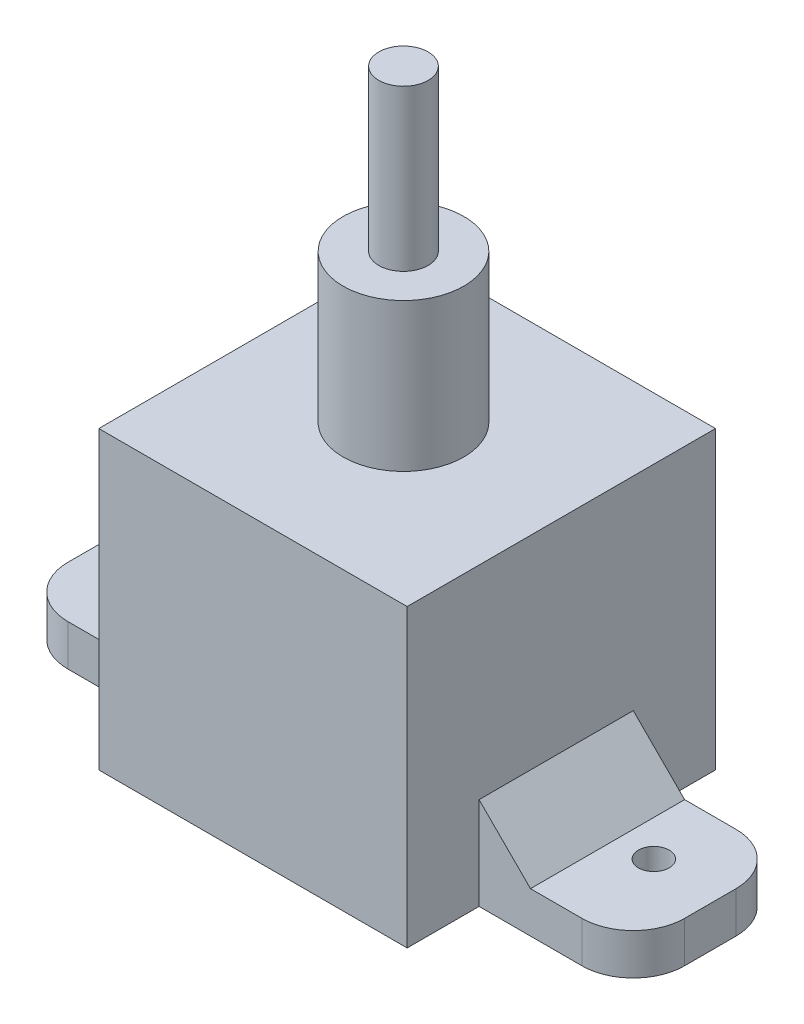
SolidWorks part; units mm, degrees
ref_plane "Спереди" through (0, 0, 0) normal (0, 0, 1) x (1, 0, 0)
ref_plane "Сверху" through (0, 0, 0) normal (0, 1, 0) x (1, 0, 0)
ref_plane "Справа" through (0, 0, 0) normal (1, 0, 0) x (0, 0, -1)
other "Configuration Table"
sketch "Эскиз1" plane through (0, 0, 0) normal (0, 1, 0) x (1, 0, 0)
  line L1 (-14.2865, 14.6433) -> (15.7135, 14.6433)
  line L2 (-14.2865, 14.6433) -> (-14.2865, -15.3567)
  line L3 (-14.2865, -15.3567) -> (15.7135, -15.3567)
  line L4 (15.7135, 14.6433) -> (15.7135, -15.3567)
  dimension "D1" = 30
  dimension "D2" = 30
extrude "высота " add sketch "Эскиз1" along normal blind 28.77
sketch "Эскиз2" plane through (0, 28.77, 0) normal (0, 1, 0) x (1, 0, 0)
  circle A0 centre (0, 0) radius 5.875
  dimension "D1" = 11.75
sketch "Эскиз3" plane through (0, 0, 0) normal (0, 0, 1) x (1, 0, 0)
  line L0 (0, 49.97) -> (0, -1.7648) construction
extrude "Бобышка-Вытянуть2" add sketch "Эскиз2" along normal blind 14.4 contours A0
sketch "Эскиз4" plane through (0, 43.17, 0) normal (0, 1, 0) x (1, 0, 0)
  circle A0 centre (0, 0) radius 2.4
  dimension "D1" = 4.8
extrude "Бобышка-Вытянуть3" add sketch "Эскиз4" along normal blind 15.6
sketch "Эскиз5" plane through (0, 0, 0) normal (0, -1, 0) x (1, 0, 0)
  line L0 (15.7135, 15.3567) -> (15.7135, -14.6433) construction
  line L1 (15.7135, 8.3567) -> (25.7135, 8.3567)
  line L2 (15.7135, 8.3567) -> (15.7135, -6.6433)
  line L3 (15.7135, -6.6433) -> (25.7135, -6.6433)
  line L4 (30.7135, 3.3567) -> (30.7135, -1.6433)
  line L5 (15.7135, -14.6433) -> (-14.2865, -14.6433) construction
  line L6 (0, 0) -> (0, -14.6433) construction
  line L12 (-14.2865, -14.6433) -> (-14.2865, 15.3567) construction
  line L13 (-14.2865, 8.3567) -> (-24.2865, 8.3567)
  line L14 (-14.2865, 8.3567) -> (-14.2865, -6.6433)
  line L15 (-14.2865, -6.6433) -> (-24.2865, -6.6433)
  line L16 (-29.2865, 3.3567) -> (-29.2865, -1.6433)
  arc A0 (-29.2865, 3.3567) -> (-24.2865, 8.3567) centre (-24.2865, 3.3567) cw
  arc A1 (-24.2865, -6.6433) -> (-29.2865, -1.6433) centre (-24.2865, -1.6433) cw
  arc A2 (30.7135, 3.3567) -> (25.7135, 8.3567) centre (25.7135, 3.3567) ccw
  arc A3 (30.7135, -1.6433) -> (25.7135, -6.6433) centre (25.7135, -1.6433) cw
  point P19 (-29.2865, 8.3567)
  point P22 (-29.2865, -6.6433)
  point P25 (30.7135, 8.3567)
  point P28 (30.7135, -6.6433)
  dimension "D7" = 5
  dimension "D8" = 5
  dimension "D9" = 5
  dimension "D10" = 5
  dimension "D1" = 15
  dimension "D2" = 15
  dimension "D3" = 8
  dimension "D4" = 15
  dimension "D5" = 15
  dimension "D6" = 8
extrude "Бобышка-Вытянуть4" add sketch "Эскиз5" against normal blind 4
sketch "Эскиз6" plane through (0, 4, 0) normal (0, 1, 0) x (1, 0, 0)
  line L0 (30.7135, 1.6433) -> (30.7135, -3.3567) construction
  line L1 (15.7135, 6.6433) -> (25.7135, 6.6433) construction
  line L2 (-24.2865, 6.6433) -> (-14.2865, 6.6433) construction
  line L3 (-29.2865, -3.3567) -> (-29.2865, 1.6433) construction
  circle A0 centre (24.2135, 0.1433) radius 1.5
  circle A1 centre (-22.7865, 0.1433) radius 1.5
  dimension "D1" = 3
  dimension "D4" = 3
  dimension "D2" = 6.5
  dimension "D3" = 6.5
  dimension "D5" = 6.5
  dimension "D6" = 6.5
extrude "Вырез-Вытянуть2" cut sketch "Эскиз6" against normal through all both and the other way through all contours A1 | A0
chamfer "Фаска2" distance 5 angle 45 1 edges at (15.7135, 4, 0.8567)
chamfer "Фаска3" distance 5 angle 45 1 edges at (-14.2865, 4, 0.8567)
